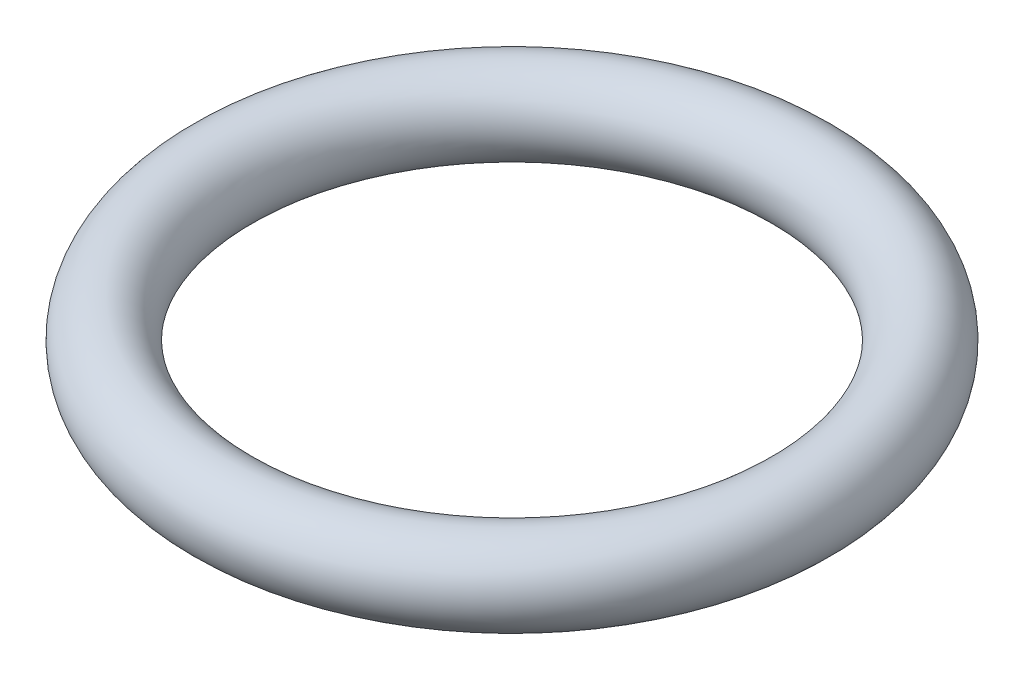
SolidWorks part; units mm, degrees
material "BUTYL"
ref_plane "Front" through (0, 0, 0) normal (0, 0, 1) x (1, 0, 0)
ref_plane "Top" through (0, 0, 0) normal (0, 1, 0) x (1, 0, 0)
ref_plane "Right" through (0, 0, 0) normal (1, 0, 0) x (0, 0, -1)
ref_axis "Axis1" through (0, 6.9999, 0) along (0, -1, 0)
sketch "Sketch1" plane through (0, 0, 0) normal (0, 0, 1) x (1, 0, 0)
  line L0 (0, 0) -> (0, -2.2319) construction
  circle A0 centre (5.3848, 0) radius 0.762
  dimension "D1" = 1.524
  dimension "D2" = 9.2456
revolve "Revolve1" add sketch "Sketch1" angle 360 about L0
